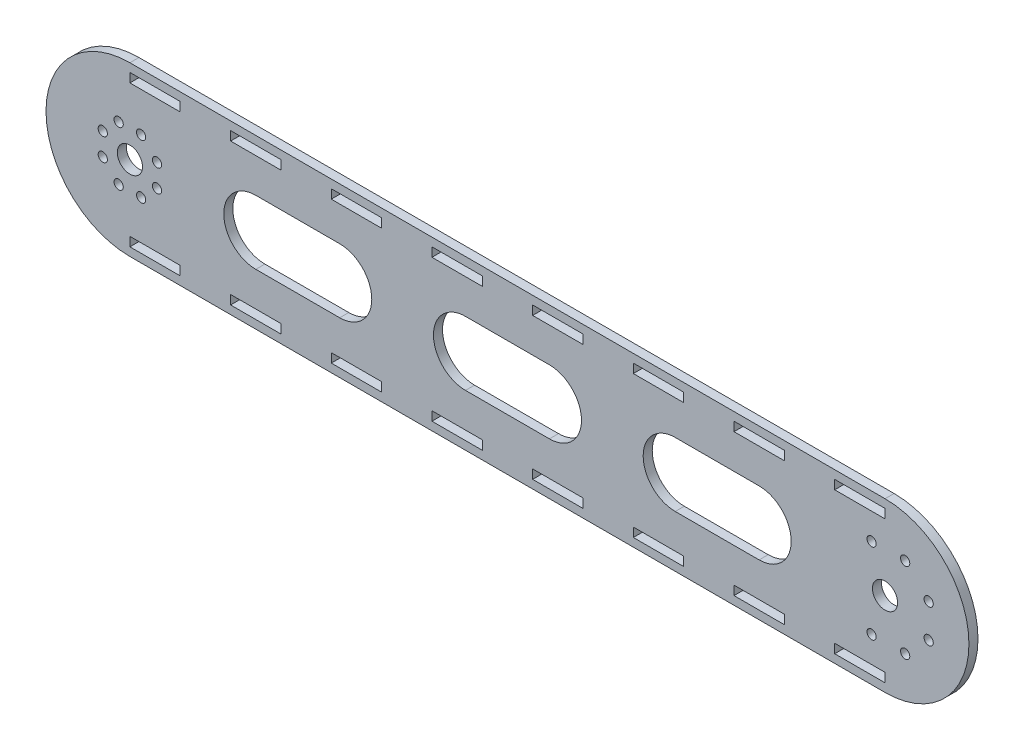
SolidWorks part; units mm, degrees
ref_plane "Front Plane" through (0, 0, 0) normal (0, 0, 1) x (1, 0, 0)
ref_plane "Top Plane" through (0, 0, 0) normal (0, 1, 0) x (1, 0, 0)
ref_plane "Right Plane" through (0, 0, 0) normal (1, 0, 0) x (0, 0, -1)
sketch "Sketch3" plane through (0, 0, 0) normal (0, 0, 1) x (1, 0, 0)
  line L0 (-20.9627, 0) -> (429.0373, 0) construction
  line L1 (-20.9627, 50) -> (429.0373, 50)
  line L2 (-20.9627, -50) -> (429.0373, -50)
  line L3 (179.0373, 0) -> (229.0373, 0) construction
  line L4 (179.0373, 19.0946) -> (229.0373, 19.0946)
  line L5 (179.0373, -19.0946) -> (229.0373, -19.0946)
  line L9 (-20.9627, 0) -> (-4.7949, 6.697)
  line L10 (-20.9627, 0) -> (-4.7949, 6.697) construction
  line L11 (-20.9627, 0) -> (-4.7949, -6.697) construction
  line L36 (-101.4371, 0) -> (436.7316, 0) construction
  line L64 (304.0053, 0) -> (354.0053, 0) construction
  line L65 (304.0053, 19.0946) -> (354.0053, 19.0946)
  line L66 (304.0053, -19.0946) -> (354.0053, -19.0946)
  line L67 (54.0693, 0) -> (104.0693, 0) construction
  line L68 (54.0693, 19.0946) -> (104.0693, 19.0946)
  line L69 (54.0693, -19.0946) -> (104.0693, -19.0946)
  line L99 (385.0007, 50) -> (385.0007, 44.46)
  arc A0 (-20.9627, 50) -> (-20.9627, -50) centre (-20.9627, 0) ccw
  arc A1 (429.0373, -50) -> (429.0373, 50) centre (429.0373, 0) ccw
  circle A2 centre (-20.9627, 0) radius 7.5
  circle A3 centre (429.0373, 0) radius 7.5
  arc A4 (179.0373, 19.0946) -> (179.0373, -19.0946) centre (179.0373, 0) ccw
  arc A5 (229.0373, -19.0946) -> (229.0373, 19.0946) centre (229.0373, 0) ccw
  circle A8 centre (-4.7949, 6.697) radius 2.75
  circle A9 centre (-4.7949, -6.697) radius 2.75
  circle A10 centre (-14.2658, -16.1679) radius 2.75
  circle A11 centre (-27.6597, -16.1679) radius 2.75
  circle A12 centre (-37.1306, -6.697) radius 2.75
  circle A13 centre (-37.1306, 6.697) radius 2.75
  circle A14 centre (-27.6597, 16.1679) radius 2.75
  circle A15 centre (-14.2658, 16.1679) radius 2.75
  circle A16 centre (455.0373, 10) radius 2.75
  circle A17 centre (441.0373, 24) radius 2.75
  circle A18 centre (421.0373, 24) radius 2.75
  circle A19 centre (455.0373, -10) radius 2.75
  circle A20 centre (441.0373, -24) radius 2.75
  circle A21 centre (421.0373, -24) radius 2.75
  arc A22 (304.0053, 19.0946) -> (304.0053, -19.0946) centre (304.0053, 0) ccw
  arc A23 (354.0053, -19.0946) -> (354.0053, 19.0946) centre (354.0053, 0) ccw
  arc A24 (54.0693, 19.0946) -> (54.0693, -19.0946) centre (54.0693, 0) ccw
  arc A25 (104.0693, -19.0946) -> (104.0693, 19.0946) centre (104.0693, 0) ccw
  point P3 (204.0373, 0)
  point P14 (204.0373, 0)
  point P59 (329.0053, 0)
  point P66 (79.0693, 0)
  dimension "D2" = 50
  dimension "D3" = 15
  dimension "D4" = 15
  dimension "D7" = 5.5
  dimension "D21" = 5.5
  dimension "D22" = 5.5
  dimension "D23" = 5.5
  dimension "D1" = 450
  dimension "D5" = 17.5
  dimension "D6" = 22.5
  dimension "D9" = 45
  dimension "D15" = 24
  dimension "D16" = 24
  dimension "D17" = 8
  dimension "D18" = 20
  dimension "D19" = 26
  dimension "D20" = 10
  dimension "D24" = 50
  dimension "D25" = 0
  dimension "D26" = 2
  dimension "D14" = 2
  dimension "D8" = 8
extrude "Boss-Extrude1" add sketch "Sketch3" along normal blind 5.4 contours L2 A1 L1 A0 A25 L69 A24 L68 A23 L66 A22 L65 A20 A3 A5 L5 A4 L4 A8 | L1 | L1 | L1 | L1 | L1 | L99 L1 | L99 region at (182.019, 44.4098, 0)
sketch "Sketch4" plane through (0, 0, 5.4) normal (0, 0, 1) x (1, 0, 0)
  line L0 (-70.9627, 0) -> (479.0373, 0) construction
  line L1 (-20.9627, 50) -> (429.0373, 50) construction
  line L2 (-20.9627, 45) -> (9.0373, 45)
  line L3 (-20.9627, 45) -> (-20.9627, 39.6)
  line L4 (-20.9627, 39.6) -> (9.0373, 39.6)
  line L5 (9.0373, 45) -> (9.0373, 39.6)
  line L6 (39.0373, 45) -> (39.0373, 39.6)
  line L7 (39.0373, 45) -> (69.0373, 45)
  line L8 (69.0373, 45) -> (69.0373, 39.6)
  line L9 (39.0373, 39.6) -> (69.0373, 39.6)
  line L10 (99.0373, 45) -> (99.0373, 39.6)
  line L11 (99.0373, 45) -> (129.0373, 45)
  line L12 (129.0373, 45) -> (129.0373, 39.6)
  line L13 (99.0373, 39.6) -> (129.0373, 39.6)
  line L14 (159.0373, 45) -> (159.0373, 39.6)
  line L15 (159.0373, 45) -> (189.0373, 45)
  line L16 (189.0373, 45) -> (189.0373, 39.6)
  line L17 (159.0373, 39.6) -> (189.0373, 39.6)
  line L18 (219.0373, 45) -> (219.0373, 39.6)
  line L19 (219.0373, 45) -> (249.0373, 45)
  line L20 (249.0373, 45) -> (249.0373, 39.6)
  line L21 (219.0373, 39.6) -> (249.0373, 39.6)
  line L22 (279.0373, 45) -> (279.0373, 39.6)
  line L23 (279.0373, 45) -> (309.0373, 45)
  line L24 (309.0373, 45) -> (309.0373, 39.6)
  line L25 (279.0373, 39.6) -> (309.0373, 39.6)
  line L26 (339.0373, 45) -> (339.0373, 39.6)
  line L27 (339.0373, 45) -> (369.0373, 45)
  line L28 (369.0373, 45) -> (369.0373, 39.6)
  line L29 (339.0373, 39.6) -> (369.0373, 39.6)
  line L30 (399.0373, 45) -> (399.0373, 39.6)
  line L31 (399.0373, 45) -> (429.0373, 45)
  line L32 (429.0373, 45) -> (429.0373, 39.6)
  line L33 (399.0373, 39.6) -> (429.0373, 39.6)
  line L34 (399.0373, -45) -> (429.0373, -45)
  line L35 (429.0373, -45) -> (429.0373, -39.6)
  line L36 (399.0373, -39.6) -> (429.0373, -39.6)
  line L37 (399.0373, -45) -> (399.0373, -39.6)
  line L38 (339.0373, -45) -> (369.0373, -45)
  line L39 (369.0373, -45) -> (369.0373, -39.6)
  line L40 (339.0373, -39.6) -> (369.0373, -39.6)
  line L41 (339.0373, -45) -> (339.0373, -39.6)
  line L42 (279.0373, -45) -> (309.0373, -45)
  line L43 (309.0373, -45) -> (309.0373, -39.6)
  line L44 (279.0373, -39.6) -> (309.0373, -39.6)
  line L45 (279.0373, -45) -> (279.0373, -39.6)
  line L46 (219.0373, -45) -> (249.0373, -45)
  line L47 (249.0373, -45) -> (249.0373, -39.6)
  line L48 (219.0373, -39.6) -> (249.0373, -39.6)
  line L49 (219.0373, -45) -> (219.0373, -39.6)
  line L50 (159.0373, -45) -> (189.0373, -45)
  line L51 (189.0373, -45) -> (189.0373, -39.6)
  line L52 (159.0373, -39.6) -> (189.0373, -39.6)
  line L53 (159.0373, -45) -> (159.0373, -39.6)
  line L54 (99.0373, -45) -> (129.0373, -45)
  line L55 (129.0373, -45) -> (129.0373, -39.6)
  line L56 (99.0373, -39.6) -> (129.0373, -39.6)
  line L57 (99.0373, -45) -> (99.0373, -39.6)
  line L58 (39.0373, -45) -> (69.0373, -45)
  line L59 (69.0373, -45) -> (69.0373, -39.6)
  line L60 (39.0373, -39.6) -> (69.0373, -39.6)
  line L61 (39.0373, -45) -> (39.0373, -39.6)
  line L62 (-20.9627, -39.6) -> (9.0373, -39.6)
  line L63 (9.0373, -45) -> (9.0373, -39.6)
  line L64 (-20.9627, -45) -> (9.0373, -45)
  line L65 (-20.9627, -45) -> (-20.9627, -39.6)
  arc A0 (-20.9627, 50) -> (-20.9627, -50) centre (-20.9627, 0) ccw construction
  arc A1 (429.0373, -50) -> (429.0373, 50) centre (429.0373, 0) ccw construction
  dimension "D1" = 30
  dimension "D2" = 5.4
  dimension "D3" = 0
  dimension "D4" = 5
  dimension "D5" = 8
extrude "Cut-Extrude1" cut sketch "Sketch4" against normal through all
